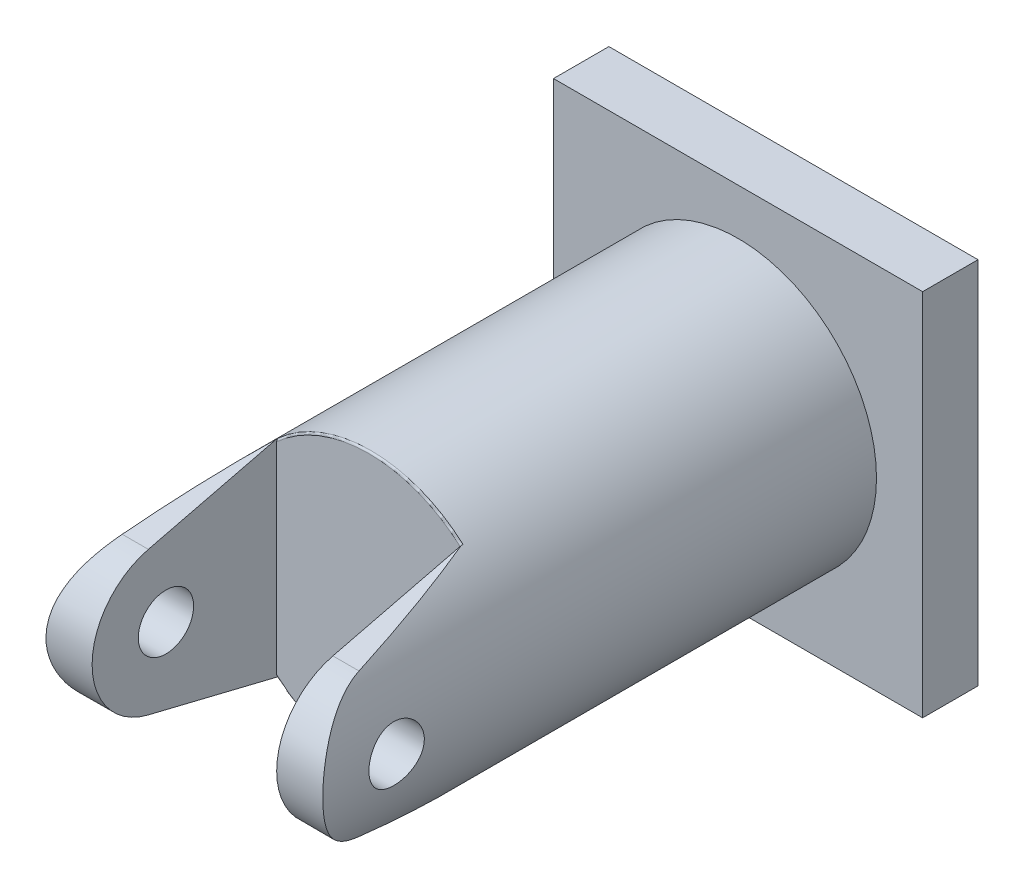
SolidWorks part; units mm, degrees
ref_plane "Ön Düzlem" through (0, 0, 0) normal (0, 0, 1) x (1, 0, 0)
ref_plane "Üst Düzlem" through (0, 0, 0) normal (0, 1, 0) x (1, 0, 0)
ref_plane "Sağ Düzlem" through (0, 0, 0) normal (1, 0, 0) x (0, 0, -1)
sketch "Sketch1" plane through (0, 0, 0) normal (0, 0, 1) x (1, 0, 0)
  circle A0 centre (0, 0) radius 7.5
  dimension "D1" = 15
extrude "Boss-Extrude1" add sketch "Sketch1" along normal blind 30
sketch "Sketch3" plane through (0, 0, 30) normal (0, 0, 1) x (1, 0, 0)
  line L1 (5, 8) -> (-5, 8)
  line L2 (5, 8) -> (5, -8)
  line L3 (5, -8) -> (-5, -8)
  line L4 (-5, 8) -> (-5, -8)
  line L5 (5, 8) -> (-5, -8) construction
  line L6 (5, -8) -> (-5, 8) construction
  point P0 (0, 0)
  dimension "D1" = 16
  dimension "D2" = 10
extrude "Cut-Extrude2" cut sketch "Sketch3" against normal blind 10
sketch "Sketch4" plane through (0, 0, 0) normal (1, 0, 0) x (0, 0, -1)
  line L0 (-20, 7.5) -> (-20, 5.5902)
  line L1 (-20, 5.5902) -> (-26.9529, 3.8847)
  line L2 (-20, -7.5) -> (-20, -5.5902)
  line L3 (-20, -5.5902) -> (-26.9527, -3.885)
  line L4 (-30, 5.5902) -> (-30, -5.5902) construction
  line L5 (-30, -5.5902) -> (-20, -5.5902) construction
  arc A0 (-26.9529, 3.8847) -> (-26.9527, -3.885) centre (-26, -0.0002) ccw
  dimension "D1" = 4
  dimension "D2" = 5.59
extrude "Cut-Extrude3" cut sketch "Sketch4" against normal through all both and the other way through all
sketch "Sketch5" plane through (0, 0, 0) normal (1, 0, 0) x (0, 0, -1)
  circle A0 centre (-26, -0.0002) radius 1.5
  arc A1 (-26.9529, 3.8847) -> (-26.9527, -3.885) centre (-26, -0.0002) ccw construction
  dimension "D1" = 3
extrude "Cut-Extrude4" cut sketch "Sketch5" against normal through all both and the other way through all
fillet "Fillet1" radius 0.1 2 edges at (0, -7.5, 20) (0, 7.5, 20)
sketch "Sketch6" plane through (0, 0, 0) normal (0, 0, -1) x (-1, 0, 0)
  line L1 (10, 10) -> (-10, 10)
  line L2 (10, 10) -> (10, -10)
  line L3 (10, -10) -> (-10, -10)
  line L4 (-10, 10) -> (-10, -10)
  line L5 (10, 10) -> (-10, -10) construction
  line L6 (10, -10) -> (-10, 10) construction
  point P0 (0, 0)
  dimension "D1" = 20
  dimension "D2" = 20
extrude "Boss-Extrude2" add sketch "Sketch6" along normal blind 3
